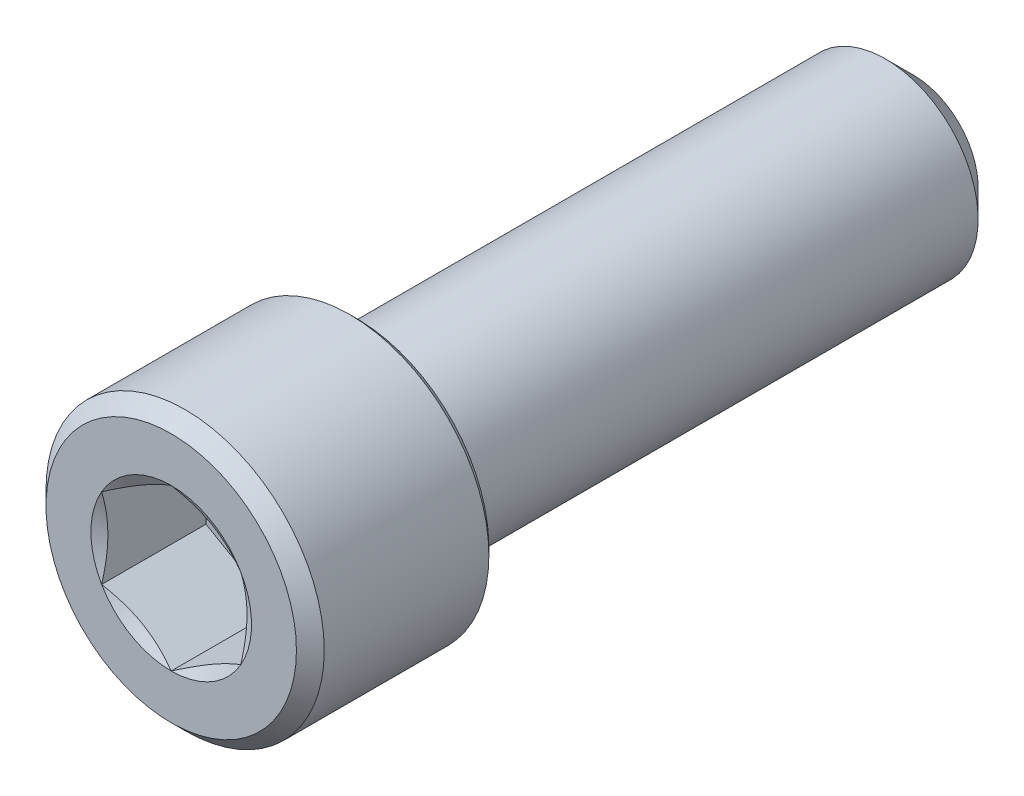
SolidWorks part; units mm, degrees
ref_plane "Front Plane" through (0, 0, 0) normal (0, 0, 1) x (1, 0, 0)
ref_plane "Top Plane" through (0, 0, 0) normal (0, 1, 0) x (1, 0, 0)
ref_plane "Right Plane" through (0, 0, 0) normal (1, 0, 0) x (0, 0, -1)
sketch "Sketch1" plane through (0, 0, 0) normal (1, 0, 0) x (0, 0, -1)
  line L0 (12.7, 0) -> (-12.7, 0) construction
  line L1 (-12.7, 0) -> (-12.7, 4.7625) construction
  line L2 (-6.35, 3.175) -> (-6.35, 0) construction
  line L3 (11.43, 0) -> (11.43, 1.27) construction
  line L4 (-6.35, 0) -> (-6.35, -3.175) construction
  point P6 (-12.7, 2.3812)
  point P9 (-12.7, -2.3813)
  point P10 (-6.35, 0)
  point P13 (8.255, -3.175)
  dimension "D1" = 1.27
  dimension "D2" = 4.445
sketch "Sketch2" plane through (0, 0, 0) normal (1, 0, 0) x (0, 0, -1)
  line L0 (12.7, 2.2225) -> (11.7475, 3.175)
  line L1 (-12.7, 4.7625) -> (-6.35, 4.7625)
  line L2 (-12.7, 4.7625) -> (-12.7, 0)
  line L4 (-6.35, 4.7625) -> (-6.35, 3.175)
  line L5 (-6.35, 3.175) -> (11.7475, 3.175)
  line L8 (12.7, 2.2225) -> (12.7, 0)
  line L9 (12.7, 0) -> (-12.7, 0) construction
  line L10 (12.7, 0) -> (-12.7, 0)
  dimension "D1" = 135
  dimension "D2" = 0.9525
revolve "Revolve1" add sketch "Sketch2" angle 360 about L10
sketch "Sketch4" plane through (0, 0, 12.7) normal (0, 0, 1) x (1, 0, 0)
  line L1 (0, 2.7496) -> (-2.3813, 1.3748)
  line L2 (-2.3813, 1.3748) -> (-2.3812, -1.3748)
  line L3 (-2.3812, -1.3748) -> (0, -2.7496)
  line L4 (0, -2.7496) -> (2.3813, -1.3748)
  line L5 (2.3813, -1.3748) -> (2.3813, 1.3748)
  line L6 (2.3813, 1.3748) -> (0, 2.7496)
  circle A0 centre (0, 0) radius 2.3813 construction
  circle A1 centre (0, 0) radius 4.7625 construction
  circle A2 centre (0, 0) radius 4.7625 construction
  dimension "D1" = 4.7625
extrude "Cut-Extrude1" cut sketch "Sketch4" against normal blind 3.5719
sketch "Sketch5" plane through (0, 0, 12.7) normal (0, 0, 1) x (1, 0, 0)
  circle A0 centre (0, 0) radius 2.7496
extrude "Cut-Extrude2" cut sketch "Sketch5" against normal blind 10 draft 60
chamfer "Chamfer1" distance 0.4763 angle 45 1 edges at (-4.7625, 0, 12.7)
chamfer "Chamfer2" distance 0.2381 angle 45 1 edges at (-4.7625, 0, 6.35)
sketch "Sketch3" [suppressed] plane through (0, 0, -12.7) normal (0, 0, -1) x (-1, 0, 0)
  circle A0 centre (0, 0) radius 3.175 construction
  circle A1 centre (0, 0) radius 3.175
ref_axis "Center Axis1" through (0, 0, -5.7312) along (0, 0, 1)
ref_plane "Contact Plane1" through (0, 0, -12.7) normal (0, 0, 1) x (1, 0, 0)
ref_plane "Contact Plane2" through (0, 0, 6.35) normal (0, 0, 1) x (1, 0, 0)
split "Split1" [suppressed] bodies to split 106
curve "Helix/Spiral1" [suppressed] pitch 1.27 height 20.32 turns 16
sketch "Sketch7" [suppressed] plane through (0, 0, 0) normal (1, 0, 0) x (0, 0, -1)
  line L0 (12.6206, 3.3125) -> (13.2556, 2.2126) construction
  line L1 (13.2556, 2.2126) -> (13.8906, 3.3125) construction
  line L2 (13.8906, 3.3125) -> (12.6206, 3.3125) construction
  line L3 (12.7, 3.175) -> (13.8113, 3.175)
  line L4 (13.2556, 3.3125) -> (13.2556, 3.175) construction
  line L5 (13.2556, 3.175) -> (13.2556, 2.3501) construction
  line L6 (13.2556, 2.3501) -> (13.2556, 2.2126) construction
  line L7 (13.1763, 2.3501) -> (13.335, 2.3501)
  line L8 (12.6603, 3.2437) -> (13.8509, 3.2437) construction
  line L9 (13.335, 2.3501) -> (13.8113, 3.175)
  line L10 (13.1763, 2.3501) -> (12.7, 3.175)
  point P0 (13.2556, 3.2437)
  dimension "D1" = 1.27
  dimension "D2" = 0.1588
sweep "Cut-Sweep1" [suppressed] cut profiles "Sketch7" path "Helix/Spiral1"
sketch "Sketch11" [suppressed] plane through (0, 0, 6.35) normal (0, 0, -1) x (-1, 0, 0)
  circle A0 centre (0, 0) radius 3.175
extrude "Boss-Extrude4" [suppressed] add sketch "Sketch11" along normal through all draft 45
sketch "Sketch9" [suppressed] plane through (0, 0, 6.35) normal (0, 0, -1) x (-1, 0, 0)
  line L0 (0, 0) -> (0, 4.7625) construction
  line L1 (0, 4.5244) -> (-0.4992, 5.0006)
  line L2 (-0.4992, 5.0006) -> (0.4992, 5.0006)
  line L3 (0.4992, 5.0006) -> (0, 4.5244)
  line L4 (-0.2496, 4.7625) -> (0, 0) construction
  line L5 (0, 0) -> (0.2496, 4.7625) construction
  circle A0 centre (0, 0) radius 4.7625 construction
  circle A1 centre (0, 0) radius 4.5244 construction
  dimension "D1" = 0.4762
  dimension "D2" = 6
extrude "Cut-Extrude3" [suppressed] cut sketch "Sketch9" against normal up to next
pattern_circular "CirPattern1" [suppressed] count 60 over 360 of bodies 112
equation "\"D1@Sketch1\"=\"Pitch@Sketch1\""
equation "\"D2@Sketch2\"=\"D1@Sketch1\"*.75"
equation "\"D4@Helix/Spiral1\"=\"Pitch@Sketch1\""
equation "\"D3@Helix/Spiral1\"=\"Length@Sketch1\"+\"Pitch@Sketch1\""
equation "\"D1@Sketch4\" = \"Drive Size@Sketch1\""
equation "\"D1@Cut-Extrude1\"=\"D1@Sketch4\"*.75"
equation "\"D19\"= \"D1@Sketch4\" * .75"
equation "\"D1@Chamfer1\" = \"Head Diameter@Sketch1\" * .05"
equation "\"D1@Chamfer2\"=\"D1@Chamfer1\"/2"
equation "\"D2@Sketch7\"=\"D1@Sketch7\"/8"
equation "\"D1@Sketch7\"=\"D4@Helix/Spiral1\""
equation "\"D2@Sketch1\"=\"Pitch@Sketch1\"*3.5"
equation "\"D1@Sketch9\"=\"D1@Chamfer1\""
equation "\"D1@CirPattern1\"=\"D3@CirPattern1\"/\"D2@Sketch9\""
